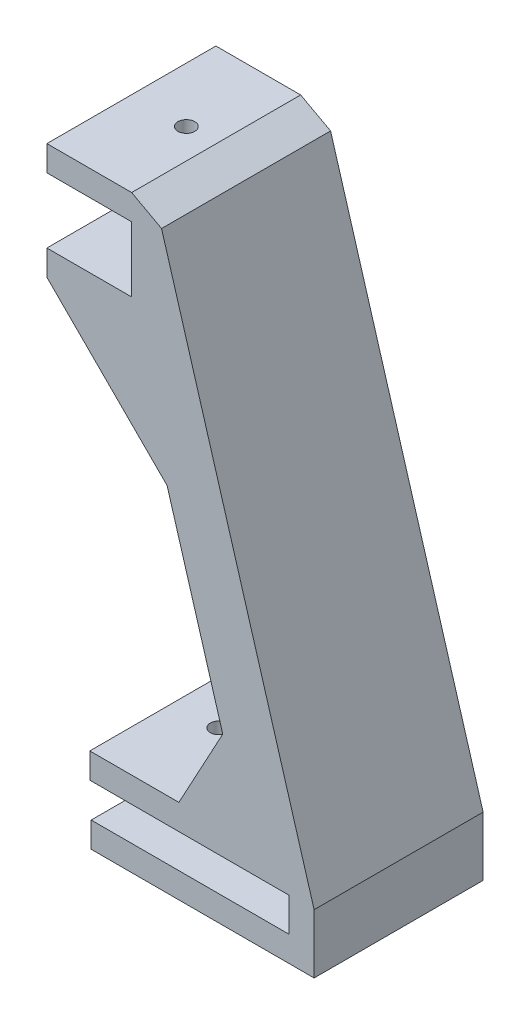
SolidWorks part; units mm, degrees
ref_plane "Front Plane" through (0, 0, 0) normal (0, 0, 1) x (1, 0, 0)
ref_plane "Top Plane" through (0, 0, 0) normal (0, 1, 0) x (1, 0, 0)
ref_plane "Right Plane" through (0, 0, 0) normal (1, 0, 0) x (0, 0, -1)
sketch "Sketch1" plane through (0, 0, 0) normal (0, 0, 1) x (1, 0, 0)
  line L0 (0, 0) -> (23.377, 0)
  line L1 (23.377, 0) -> (23.377, 4)
  line L2 (23.377, 4) -> (-0.1661, 4)
  line L3 (0, 0) -> (0, -3)
  line L4 (0, -3) -> (26.377, -3)
  line L5 (26.377, -3) -> (26.377, 4)
  line L6 (26.377, 4) -> (7.7557, 66.7)
  line L7 (7.7557, 66.7) -> (-5.2443, 66.7)
  line L8 (-5.2443, 66.7) -> (-5.2443, 63.7)
  line L9 (-5.2443, 63.7) -> (4.7557, 63.7)
  line L10 (4.7557, 63.7) -> (4.7557, 56)
  line L11 (4.7557, 56) -> (-5.2443, 56)
  line L12 (-5.2443, 56) -> (-5.2443, 53)
  line L13 (-5.2443, 53) -> (4.7557, 53)
  line L14 (4.7557, 53) -> (18.4173, 7)
  line L15 (4.7557, 7) -> (-0.1661, 7)
  line L16 (-0.1661, 7) -> (-0.1661, 4)
  line L17 (18.4173, 7) -> (4.7557, 7)
  dimension "D1" = 52
  dimension "D2" = 3
  dimension "D3" = 4
  dimension "D4" = 7.7
  dimension "D5" = 10
  dimension "D6" = 3
  dimension "D7" = 3
extrude "Boss-Extrude1" add sketch "Sketch1" along normal blind 20
chamfer "Chamfer1" distance 10 angle 45 2 edges at (4.7557, 53, 10) (18.4173, 7, 10)
sketch "Sketch2" plane through (0, 66.7, 0) normal (0, 1, 0) x (1, 0, 0)
  line L0 (-5.2443, 0) -> (7.7557, -20) construction
  circle A0 centre (1.2557, -10) radius 1
  dimension "D1" = 2
extrude "Cut-Extrude1" cut sketch "Sketch2" against normal blind 22
sketch "Sketch3" plane through (0, 7, 0) normal (0, 1, 0) x (1, 0, 0)
  line L0 (-0.1661, 0) -> (10.3743, -20) construction
  circle A0 centre (5.1041, -10) radius 1
  dimension "D1" = 2
extrude "Cut-Extrude2" cut sketch "Sketch3" against normal blind 22
chamfer "Chamfer2" distance 2 angle 45 1 edges at (7.7557, 66.7, 10)
